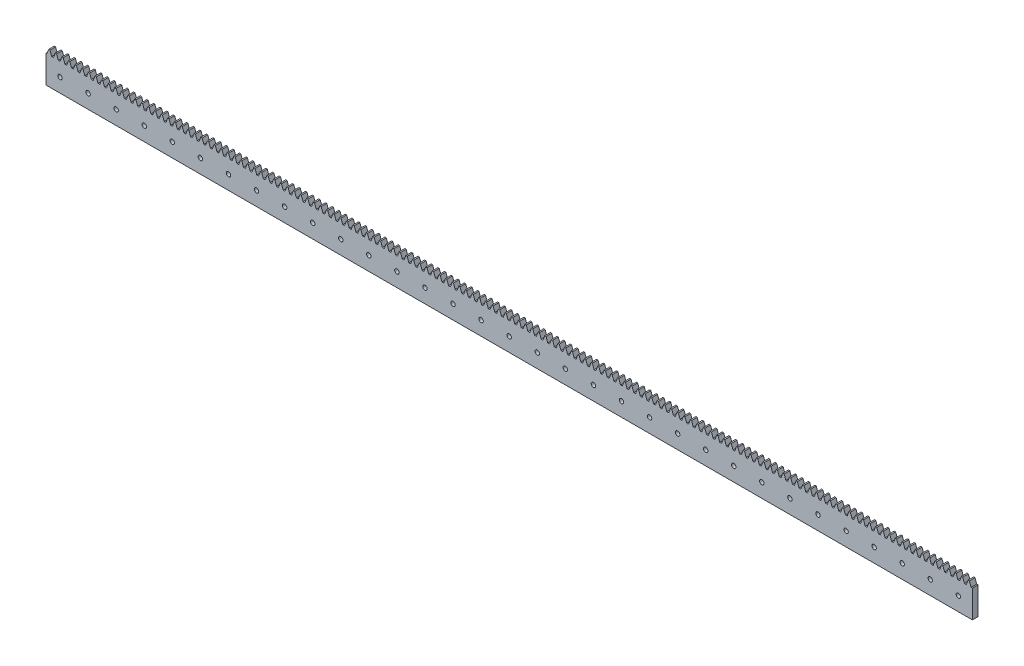
SolidWorks part; units mm, degrees
extrude "Blank" add sketch "BlankSke" against normal blind 4
sketch "BlankSke" plane through (0, 0, 0) normal (0, 0, 1) x (1, 0, 0)
  line L1 (0, 0) -> (660, 0)
  line L2 (0, 0) -> (0, 23)
  line L3 (0, 23) -> (660, 23)
  line L4 (660, 0) -> (660, 23)
  dimension "Length" = 660
ref_plane "Plane1" through (0, 0, 0) normal (0, 0, 1) x (1, 0, 0)
ref_plane "Plane2" through (0, 0, 0) normal (0, 1, 0) x (1, 0, 0)
ref_plane "Plane3" through (0, 0, 0) normal (1, 0, 0) x (0, 0, -1)
other "Configuration Table"
sketch "HoldingSke" plane through (0, 0, 0) normal (0, 1, 0) x (1, 0, 0)
  line L0 (0, 0) -> (0.0928, 0.6602)
  line L1 (-15, 0) -> (100, 0) construction
  line L2 (0, 0) -> (-2.1039, 2.3779)
  line L3 (0, 0) -> (-11.863, 4.5341)
  line L4 (0, 0) -> (-6.8053, 5.3169)
  line L5 (0, 0) -> (-23.7986, -8.8762)
  line L6 (0, 0) -> (-10.5278, -7.1032)
  line L9 (-71.009, 38.7566) -> (549.1882, 264.4899)
  line L10 (-76.2, 3.8779) -> (-54.7, 3.8779)
  line L11 (0, 0) -> (-4, 0)
  line L12 (-76.2, 101.6) -> (-76.147, 101.6)
  line L13 (24.9733, 27.94) -> (52.9518, 28.4284)
  line L14 (24.9733, 27.94) -> (24.9743, 27.94)
  line L15 (24.9733, 27.94) -> (100.4006, 29.5858)
  circle A0 centre (0, 0) radius 19.05
  circle A1 centre (0, 0) radius 10.75
  circle A2 centre (0, 0) radius 12.7
  dimension "Num_teeth" = 142
  dimension "Width" = 4
  dimension "Length" = 660
  dimension "Pitch_height" = 21.5
sketch "TooCutSkeIll" plane through (0, 0, 0) normal (0, 0, 1) x (1, 0, 0)
  line L0 (-1.8687, 22.9605) -> (-0.7447, 19.8724)
  line L1 (-0.3914, 19.625) -> (0.3914, 19.625)
  line L2 (0.7447, 19.8724) -> (1.8687, 22.9605)
  line L3 (660, 23) -> (0, 23) construction
  line L4 (0, 0) -> (0, 64.897) construction
  line L5 (-13.208, 21.5) -> (12.954, 21.5) construction
  line L6 (0, 0) -> (660, 0) construction
  line L7 (1.3371, 21.5) -> (1.3371, 48.7463) construction
  line L8 (-1.3371, 21.5) -> (-1.3371, 48.7463) construction
  line L9 (1.9251, 23) -> (1.9251, 23.0254)
  line L10 (-1.9251, 23) -> (-1.9251, 23.0254)
  line L11 (-1.9251, 23.0254) -> (1.9251, 23.0254)
  arc A0 (0.3914, 19.625) -> (0.7447, 19.8724) centre (0.3914, 20.001) ccw
  arc A1 (-0.7447, 19.8724) -> (-0.3914, 19.625) centre (-0.3914, 20.001) ccw
  arc A2 (1.9251, 23) -> (1.8687, 22.9605) centre (1.9251, 22.94) ccw
  arc A3 (-1.8687, 22.9605) -> (-1.9251, 23) centre (-1.9251, 22.94) ccw
  dimension "Addendum_plus" = 1.5254
  dimension "Pitch_height" = 21.5
  dimension "Pressure_angle" = 20
  dimension "Gap_width" = 2.6742
  dimension "Dedendum" = 1.875
extrude "ToothCutIll" [suppressed] cut sketch "TooCutSkeIll" against normal through all
sketch "TooCutSkeSim" plane through (0, 0, 0) normal (0, 0, 1) x (1, 0, 0)
  line L0 (0.6547, 19.625) -> (-0.6547, 19.625)
  line L1 (1.8923, 23.0254) -> (0.6547, 19.625)
  line L2 (0, 17.4625) -> (0, 53.467) construction
  line L3 (1.8923, 23.0254) -> (-1.8923, 23.0254)
  line L6 (-1.8923, 23.0254) -> (-0.6547, 19.625)
  line L9 (-1.3371, 21.5) -> (1.3371, 21.5) construction
  line L10 (0, 0) -> (660, 0) construction
  line L11 (1.3371, 21.5) -> (1.3371, 53.467) construction
  line L12 (-1.3371, 21.5) -> (-1.3371, 53.467) construction
  dimension "Addendum_plus" = 1.5254
  dimension "Pitch_height" = 21.5
  dimension "Pressure_angle" = 20
  dimension "Gap_width" = 2.6742
  dimension "Dedendum" = 1.875
extrude "ToothCutSim" cut sketch "TooCutSkeSim" against normal through all
pattern_linear "TeethCuts" count 142 spacing 4.7124 along (1, 0, 0) of "ToothCutIll", "ToothCutSim"
sketch "草图2" plane through (0, 0, 0) normal (0, 0, 1) x (1, 0, 0)
  line L0 (660, 0) -> (660, 19.625) construction
  line L2 (0, 0) -> (660, 0) construction
  circle A0 centre (650, 10) radius 1.575
  circle A1 centre (630, 10) radius 1.575
  circle A2 centre (610, 10) radius 1.575
  circle A3 centre (590, 10) radius 1.575
  circle A4 centre (570, 10) radius 1.575
  circle A5 centre (550, 10) radius 1.575
  circle A6 centre (530, 10) radius 1.575
  circle A7 centre (510, 10) radius 1.575
  circle A8 centre (490, 10) radius 1.575
  circle A9 centre (470, 10) radius 1.575
  circle A10 centre (450, 10) radius 1.575
  circle A11 centre (430, 10) radius 1.575
  circle A12 centre (410, 10) radius 1.575
  circle A13 centre (390, 10) radius 1.575
  circle A14 centre (370, 10) radius 1.575
  circle A15 centre (350, 10) radius 1.575
  circle A16 centre (330, 10) radius 1.575
  circle A17 centre (310, 10) radius 1.575
  circle A18 centre (290, 10) radius 1.575
  circle A19 centre (270, 10) radius 1.575
  circle A20 centre (250, 10) radius 1.575
  circle A21 centre (230, 10) radius 1.575
  circle A22 centre (210, 10) radius 1.575
  circle A23 centre (190, 10) radius 1.575
  circle A24 centre (170, 10) radius 1.575
  circle A25 centre (150, 10) radius 1.575
  circle A26 centre (130, 10) radius 1.575
  circle A27 centre (110, 10) radius 1.575
  circle A28 centre (90, 10) radius 1.575
  circle A29 centre (70, 10) radius 1.575
  circle A30 centre (50, 10) radius 1.575
  circle A31 centre (30, 10) radius 1.575
  circle A32 centre (10, 10) radius 1.575
  dimension "D4" = 3.15
  dimension "D1" = 10
  dimension "D3" = 20
  dimension "D5" = 10
  dimension "D2" = 33
extrude "切除-拉伸2" cut sketch "草图2" against normal through all
equation "' \"Module@HoldingSke\" = 6.35"
equation "' \"Num_teeth@HoldingSke\" = 12"
equation "' \"Ap@HoldingSke\" =  20"
equation "' \"Ap@HoldingSke\" = 20"
equation "' \"Width@HoldingSke\" = 0.25 * 25.4"
equation "' \"Show_teeth@HoldingSke\" = 500"
equation "' \"Backlash@HoldingSke\" = 0.009 * 25.4"
equation "' \"Addendum_fac@HoldingSke\" = 1.0"
equation "' \"Dedendum_fac@HoldingSke\" = 1.25"
equation "' \"Dedendum_add@HoldingSke\" = 0.00005 * 25.4"
equation "' \"Clearance_fac@HoldingSke\" = 0.25"
equation "' \"Pitch_height@HoldingSke\" = 1 * 25.4"
equation "' \"Length@HoldingSke\" = 4.71 * 25.4"
equation "\"Pitch@HoldingSke\" = 1 / \"Module@HoldingSke\""
equation "\"MPH@HoldingSke\" = \"Dedendum_fac@HoldingSke\" / \"Pitch@HoldingSke\" + 2 * \"Dedendum_add@HoldingSke\" + 0.002 * 25.4"
equation "\"MPH@HoldingSke\" = ((sgn( \"MPH@HoldingSke\" - \"Pitch_height@HoldingSke\")+1)*( \"MPH@HoldingSke\" - \"Pitch_height@HoldingSke\"))/2 + \"Pitch_height@HoldingSke\""
equation "\"Blank_height@BlankSke\" = \"Pitch_height@HoldingSke\" + \"Addendum_fac@HoldingSke\"  / \"Pitch@HoldingSke\" "
equation "\"Length@BlankSke\" =  \"Length@HoldingSke\""
equation "\"Face_width@Blank\" = \"Width@HoldingSke\""
equation "\"Pressure_angle@TooCutSkeIll\" = \"Ap@HoldingSke\""
equation "\"Addendum_plus@TooCutSkeIll\" =  \"Addendum_fac@HoldingSke\"  / \"Pitch@HoldingSke\" + 0.001 *25.4"
equation "\"Dedendum@TooCutSkeIll\" = \"Dedendum_fac@HoldingSke\"  / \"Pitch@HoldingSke\""
equation "\"Pitch_height@TooCutSkeIll\" =  \"MPH@HoldingSke\""
equation "\"Gap_width@TooCutSkeIll\" = 3.14159265 / 2 / \"Pitch@HoldingSke\" + 6 * \"Backlash@HoldingSke\""
equation "\"Pressure_angle@TooCutSkeSim\" = \"Ap@HoldingSke\""
equation "\"Addendum_plus@TooCutSkeSim\" =  \"Addendum_fac@HoldingSke\"  / \"Pitch@HoldingSke\" + 0.001 * 25.4"
equation "\"Dedendum@TooCutSkeSim\" = \"Dedendum_fac@HoldingSke\"  / \"Pitch@HoldingSke\""
equation "\"Pitch_height@TooCutSkeSim\" =  \"MPH@HoldingSke\""
equation "\"Gap_width@TooCutSkeSim\" = 3.14159265 / 2 / \"Pitch@HoldingSke\" + 6 * \"Backlash@HoldingSke\""
equation "\"Root_fillet@TooCutSkeIll\" = \"Clearance_fac@HoldingSke\" / \"Pitch@HoldingSke\" + \"Dedendum_add@HoldingSke\""
equation "\"Break_rad@TooCutSkeIll\" = 0.02 / \"Pitch@HoldingSke\" * 2"
equation "\"Linear_pitch@TeethCuts\" = 3.14159265 / \"Pitch@HoldingSke\""
equation "\"Num_teeth@HoldingSke\" = int( ( \"Length@HoldingSke\" + 0 ) / (3.14159265 / \"Pitch@HoldingSke\")) + 0.9999  + 1"
equation " \"Num_teeth@TeethCuts\" = int( \"Show_teeth@HoldingSke\" ) + 1"
equation " \"Num_teeth@TeethCuts\" = ((sgn( \"Num_teeth@TeethCuts\" - \"Num_teeth@HoldingSke\" )-1)*( \"Num_teeth@TeethCuts\" - \"Num_teeth@HoldingSke\" ))/-2+ \"Num_teeth@HoldingSke\""
equation " \"Num_teeth@TeethCuts\" = ((sgn( \"Num_teeth@TeethCuts\" - 2.0)+1)*( \"Num_teeth@TeethCuts\" - 2.0))/2 +2.0"
